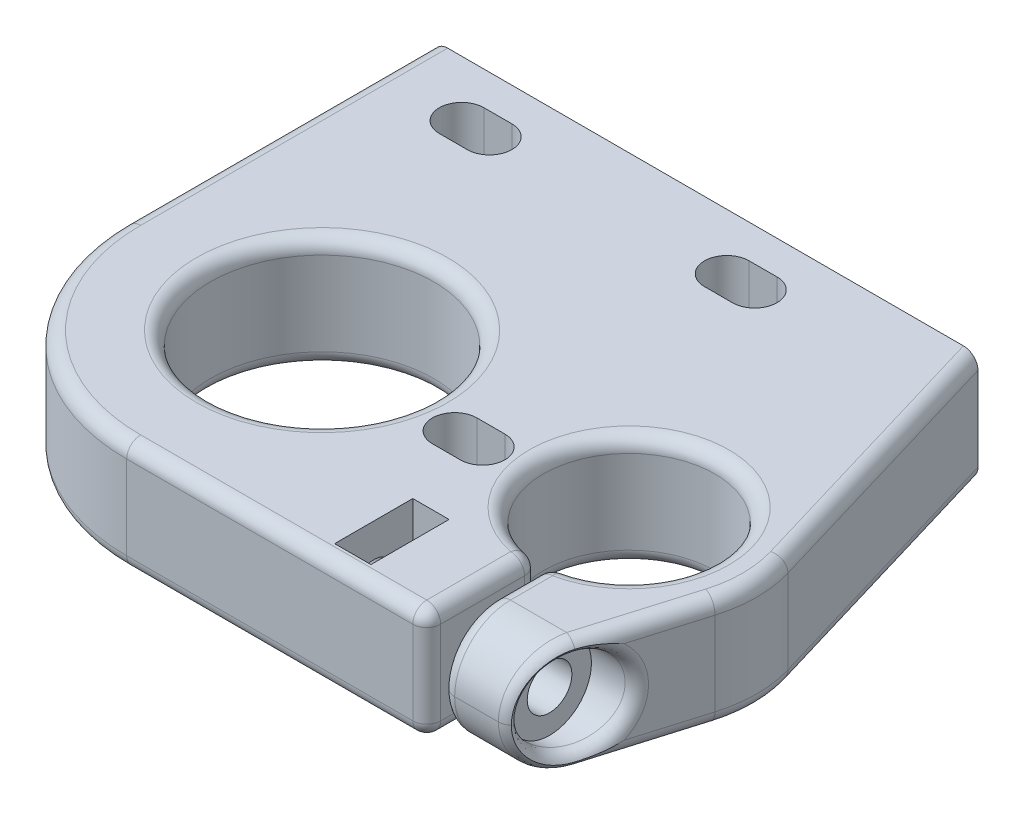
SolidWorks part; units mm, degrees
ref_plane "Спереди" through (0, 0, 0) normal (0, 0, 1) x (1, 0, 0)
ref_plane "Сверху" through (0, 0, 0) normal (0, 1, 0) x (1, 0, 0)
ref_plane "Справа" through (0, 0, 0) normal (1, 0, 0) x (0, 0, -1)
sketch "Эскиз1" plane through (0, 0, 0) normal (0, 1, 0) x (1, 0, 0)
  line L0 (36, 16) -> (36, -8.0974) construction
  line L1 (0, 36) -> (39, 36)
  line L2 (14, 0) -> (35.5, 0)
  line L3 (-36.7265, 14) -> (56.2728, 14) construction
  line L4 (39, 36) -> (44.77, 16.6097)
  line L5 (35.5, 7.8704) -> (35.5, 0)
  line L6 (41.3805, 0) -> (44.77, 11.3903)
  line L7 (0, 36) -> (0, 14)
  line L8 (36.5, 7.8704) -> (36.5, 0)
  line L9 (36.5, 0) -> (41.3805, 0)
  line L10 (-5.3449, 4) -> (57.1159, 4) construction
  line L11 (14, 14) -> (14, 39.9763) construction
  line L12 (27.7, 1.2) -> (30.3, 1.2)
  line L13 (27.7, 1.2) -> (27.7, 6.8)
  line L14 (27.7, 6.8) -> (30.3, 6.8)
  line L15 (30.3, 1.2) -> (30.3, 6.8)
  line L16 (27.7, 1.2) -> (30.3, 6.8) construction
  line L17 (27.7, 6.8) -> (30.3, 1.2) construction
  line L18 (22, 14) -> (29.85, 14) construction
  line L19 (14, 9.5488) -> (14, 43.7619) construction
  line L20 (-5.2679, 32) -> (49.731, 32) construction
  line L21 (25, 32) -> (27, 32) construction
  line L22 (25, 33.6) -> (27, 33.6)
  line L23 (25, 30.4) -> (27, 30.4)
  line L24 (6, 32) -> (8, 32) construction
  line L25 (25, 12.5) -> (27, 12.5) construction
  line L26 (25, 14.1) -> (27, 14.1)
  line L27 (25, 10.9) -> (27, 10.9)
  line L28 (6, 33.6) -> (8, 33.6)
  line L29 (6, 30.4) -> (8, 30.4)
  circle A0 centre (14, 14) radius 8
  arc A1 (36.5, 7.8704) -> (35.5, 7.8704) centre (36, 14) ccw
  arc A2 (44.77, 11.3903) -> (44.77, 16.6097) centre (36, 14) ccw
  circle A3 centre (36, 14) radius 9.15 construction
  arc A4 (0, 14) -> (14, 0) centre (14, 14) ccw
  circle A5 centre (36, 14) radius 6.15 construction
  arc A6 (25, 33.6) -> (25, 30.4) centre (25, 32) ccw
  arc A7 (27, 30.4) -> (27, 33.6) centre (27, 32) ccw
  arc A8 (6, 33.6) -> (6, 30.4) centre (6, 32) ccw
  arc A9 (25, 14.1) -> (25, 10.9) centre (25, 12.5) ccw
  arc A10 (8, 30.4) -> (8, 33.6) centre (8, 32) ccw
  arc A11 (27, 10.9) -> (27, 14.1) centre (27, 12.5) ccw
  point P23 (29, 4)
  point P37 (26, 12.5)
  point P40 (26, 32)
  point P48 (7, 32)
  point P56 (0, 0)
  point P57 (7.0914, 33.8617)
  point P59 (0, 0)
  point P60 (0, 0)
  dimension "D4" = 39
  dimension "D5" = 0.5
  dimension "D8" = 3
  dimension "D6" = 16
  dimension "D7" = 12.3
  dimension "D16" = 19
  dimension "D24" = 13
  dimension "D23" = 23.5
  dimension "D22" = 1.6
  dimension "D1" = 22
  dimension "D2" = 22
  dimension "D3" = 14
  dimension "D9" = 0.5
  dimension "D10" = 4
  dimension "D11" = 15
  dimension "D12" = 5.6
  dimension "D13" = 2.6
  dimension "D14" = 0
  dimension "D15" = 4
  dimension "D21" = 2
extrude "Бобышка-Вытянуть1" add sketch "Эскиз1" along normal blind 8
sketch "Эскиз2" plane through (27.7, 0, 0) normal (1, 0, 0) x (0, 0, -1)
  line L0 (4, 0) -> (4, 8) construction
  line L1 (6.8, 0) -> (1.2, 0) construction
  line L2 (6.8, 8) -> (1.2, 8) construction
  line L3 (1.2, 4) -> (6.8, 4) construction
  line L4 (1.2, 8) -> (1.2, 0) construction
  line L5 (6.8, 8) -> (6.8, 0) construction
  circle A0 centre (4, 4) radius 1.6
  circle A1 centre (4, 4) radius 3
  dimension "D1" = 3.2
  dimension "D2" = 6
extrude "Вырез-Вытянуть1" cut sketch "Эскиз2" along normal through all from offset 3 contours A0 region at (27.7, 4, -4) offset against normal yes
extrude "Вырез-Вытянуть2" cut sketch "Эскиз2<3>" along normal through all from offset 12.6 contours A1
sketch "Эскиз2<3>" plane through (27.7, 0, 0) normal (1, 0, 0) x (0, 0, -1) same geometry as "Эскиз2"
fillet "Скругление2" radius 4 2 edges at (38.9403, 0, 0) (38.9403, 8, 0)
fillet "Скругление3" radius 1 28 edges at (0, 8, -25) (4.1005, 8, -4.1005) (0, 0, -25) (4.1005, 0, -4.1005) (24.75, 8, 0) (24.75, 0, 0) (41.885, 0, -26.3048) (45.15, 0, -14) (43.6704, 0, -7.6952) (41.7292, 1.1716, -1.1716) (41.7292, 6.8284, -1.1716) (43.6704, 8, -7.6952) (41.885, 8, -26.3048) (36.5, 0, -5.9352) (36.5, 1.1716, -1.1716) (36.5, 6.8284, -1.1716) (14, 0, -6) (41.6781, 4, -1) (45.15, 8, -14) (36.5, 4, -7.8704) (35.5, 4, -7.8704) (35.5, 0, -3.9352) (35.5, 4, 0) (36.5, 8, -5.9352) (35.5, 8, -3.9352) (36, 0, -20.15) (36, 8, -20.15) (14, 8, -6)
